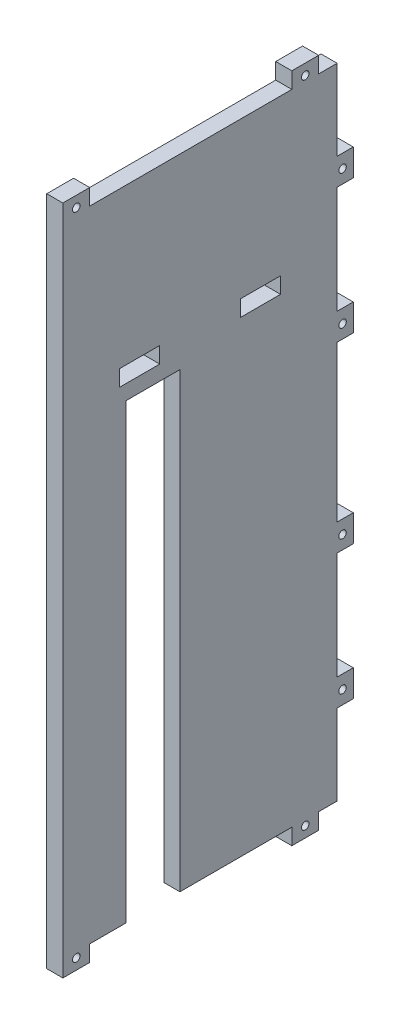
SolidWorks part; units mm, degrees
ref_plane "Plan de face" through (0, 0, 0) normal (0, 0, 1) x (1, 0, 0)
ref_plane "Plan de dessus" through (0, 0, 0) normal (0, 1, 0) x (1, 0, 0)
ref_plane "Plan de droite" through (0, 0, 0) normal (1, 0, 0) x (0, 0, -1)
sketch "Esquisse1" plane through (0, 0, 0) normal (1, 0, 0) x (0, 0, -1)
  line L0 (97.1531, 0) -> (-102.2664, 0) construction
  line L1 (-51.085, 119) -> (51.085, 119)
  line L2 (-51.085, 119) -> (-51.085, -119)
  line L3 (-51.085, -119) -> (51.085, -119)
  line L4 (51.085, 119) -> (51.085, -119)
  line L5 (0, 172.7153) -> (0, -236.1933) construction
  line L15 (-30, 61) -> (-15, 61)
  line L16 (-30, 61) -> (-30, 55)
  line L17 (-30, 55) -> (-15, 55)
  line L18 (-15, 61) -> (-15, 55)
  line L19 (15, 61) -> (30, 61)
  line L20 (15, 61) -> (15, 55)
  line L21 (15, 55) -> (30, 55)
  line L22 (30, 61) -> (30, 55)
  dimension "D1" = 238
  dimension "D2" = 102.17
  dimension "D4" = 119
  dimension "D13" = 15
  dimension "D14" = 15
  dimension "D15" = 30
  dimension "D16" = 6
  dimension "D17" = 6
  dimension "D3" = 51.085
  dimension "D5" = 58
  dimension "D6" = 21.085
extrude "Boss.-Extru.1" add sketch "Esquisse1" along normal blind 6
sketch "Esquisse3" plane through (6, 0, 0) normal (1, 0, 0) x (0, 0, -1)
  line L0 (-51.085, -119) -> (51.085, -119) construction
  line L1 (-51.085, -119) -> (-41.085, -119)
  line L2 (-51.085, -119) -> (-51.085, -125)
  line L3 (-51.085, -125) -> (-41.085, -125)
  line L4 (-41.085, -119) -> (-41.085, -125)
  line L5 (245.3741, 0) -> (-166.5298, 0) construction
  line L6 (51.085, -119) -> (51.085, 119) construction
  line L7 (34.205, -119) -> (44.205, -119)
  line L8 (34.205, -119) -> (34.205, -125)
  line L9 (34.205, -125) -> (44.205, -125)
  line L10 (0, 208.6671) -> (0, -232.3841) construction
  line L12 (44.205, -119) -> (44.205, -125)
  line L13 (51.085, 89) -> (57.085, 89)
  line L14 (51.085, 89) -> (51.085, 79)
  line L15 (51.085, 79) -> (57.085, 79)
  line L16 (57.085, 89) -> (57.085, 79)
  line L17 (51.085, 39) -> (57.085, 39)
  line L18 (51.085, 39) -> (51.085, 29)
  line L19 (51.085, 29) -> (57.085, 29)
  line L20 (57.085, 39) -> (57.085, 29)
  line L21 (57.085, -39) -> (57.085, -29)
  line L22 (51.085, -29) -> (57.085, -29)
  line L23 (51.085, -39) -> (51.085, -29)
  line L24 (51.085, -39) -> (57.085, -39)
  line L25 (57.085, -89) -> (57.085, -79)
  line L26 (51.085, -79) -> (57.085, -79)
  line L27 (51.085, -89) -> (51.085, -79)
  line L28 (51.085, -89) -> (57.085, -89)
  line L29 (0, -208.6671) -> (0, 232.3841) construction
  line L46 (44.205, 119) -> (44.205, 125)
  line L47 (34.205, 125) -> (44.205, 125)
  line L48 (34.205, 119) -> (34.205, 125)
  line L49 (34.205, 119) -> (44.205, 119)
  line L50 (-41.085, 119) -> (-41.085, 125)
  line L51 (-51.085, 125) -> (-41.085, 125)
  line L52 (-51.085, 119) -> (-51.085, 125)
  line L53 (-51.085, 119) -> (-41.085, 119)
  dimension "D2" = 10
  dimension "D3" = 6
  dimension "D4" = 10
  dimension "D5" = 6.88
  dimension "D6" = 6
  dimension "D7" = 10
  dimension "D8" = 6
  dimension "D9" = 6
  dimension "D10" = 10
extrude "Boss.-Extru.5" add sketch "Esquisse3" against normal blind 6
sketch "Esquisse4" plane through (6, 0, 0) normal (1, 0, 0) x (0, 0, -1)
  line L0 (57.085, -29) -> (51.085, -29) construction
  line L1 (57.085, -39) -> (57.085, -29) construction
  line L2 (57.085, -89) -> (57.085, -79) construction
  line L3 (57.085, -79) -> (51.085, -79) construction
  line L10 (-51.085, -125) -> (-41.085, -125) construction
  line L11 (-51.085, 125) -> (-51.085, -125) construction
  line L14 (0, 149.5198) -> (0, -197.2248) construction
  line L15 (203.7475, 0) -> (-122.4342, 0) construction
  line L16 (0, -149.5198) -> (0, 197.2248) construction
  line L17 (34.205, -119) -> (34.205, -125) construction
  line L18 (34.205, -125) -> (44.205, -125) construction
  circle A0 centre (39.205, -121) radius 1.4
  circle A1 centre (53.085, -84) radius 1.4
  circle A2 centre (53.085, -34) radius 1.4
  circle A3 centre (-46.085, 121) radius 1.4
  circle A4 centre (53.085, 34) radius 1.4
  circle A5 centre (53.085, 84) radius 1.4
  circle A8 centre (39.205, 121) radius 1.4
  circle A15 centre (-46.085, -121) radius 1.4
  point P0 (54.085, -29)
  point P35 (34.205, -122)
  dimension "D2" = 2.8
  dimension "D3" = 2.8
  dimension "D4" = 4
  dimension "D5" = 2.8
  dimension "D6" = 5
  dimension "D7" = 5
  dimension "D8" = 4
  dimension "D9" = 4
  dimension "D10" = 2.8
  dimension "D11" = 5
  dimension "D12" = 4
  dimension "D13" = 5
extrude "Enlèv. mat.-Extru.1" cut sketch "Esquisse4" against normal blind 6
sketch "Esquisse6" plane through (6, 0, 0) normal (1, 0, 0) x (0, 0, -1)
  line L0 (-41.085, -119) -> (34.205, -119) construction
  line L1 (-27.485, -119) -> (-7.485, -119)
  line L2 (-27.485, -119) -> (-27.485, 49.46)
  line L3 (-27.485, 49.46) -> (-7.485, 49.46)
  line L4 (-7.485, -119) -> (-7.485, 49.46)
  line L5 (51.085, -29) -> (51.085, 29) construction
  line L6 (-41.085, 125) -> (-51.085, 125) construction
  dimension "D1" = 20
  dimension "D2" = 75.54
  dimension "D3" = 58.57
extrude "Enlèv. mat.-Extru.2" cut sketch "Esquisse6" against normal blind 6
equation "\"D3@Esquisse1\"=\"D2@Esquisse1\"/2"
equation "\"D4@Esquisse1\"=\"D1@Esquisse1\"/2"
